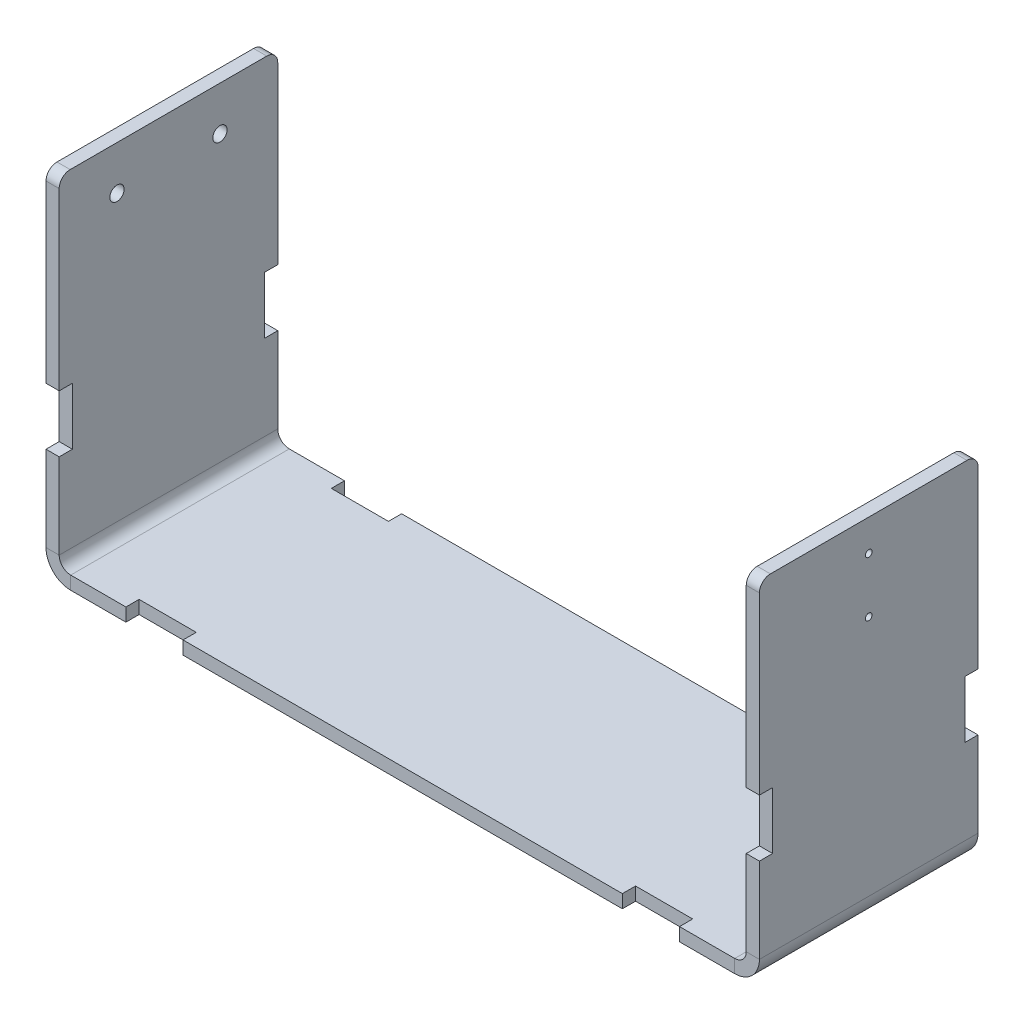
SolidWorks part; units mm, degrees
note: The reader was unsure of these and kept them because the rebuilt part matched: bend radius of "Base-Flange1", "BaseBend1", "BaseBend2".
ref_plane "Front Plane" through (0, 0, 0) normal (0, 0, 1) x (1, 0, 0)
ref_plane "Top Plane" through (0, 0, 0) normal (0, 1, 0) x (1, 0, 0)
ref_plane "Right Plane" through (0, 0, 0) normal (1, 0, 0) x (0, 0, -1)
sketch "Sketch1" plane through (0, 0, 0) normal (0, 0, 1) x (1, 0, 0)
  line L0 (79.4411, 0) -> (-79.4411, 0)
  line L1 (-79.4411, 0) -> (-79.4411, 78.6072)
  line L2 (0, -1000) -> (0, 49000) construction
  line L3 (79.4411, 0) -> (79.4411, 78.6072)
  line L4 (0, 78.6072) -> (-38.1661, 40.4411) construction
  line L5 (-1000, 78.6072) -> (49000, 78.6072) construction
  line L6 (-66.7411, -930.7018) -> (-66.7411, 49069.2982) construction
  circle A0 centre (0, 78.6072) radius 25.4 construction
  circle A1 centre (-38.1661, 40.4411) radius 28.575 construction
  circle A2 centre (0, 78.6072) radius 25.4 construction
  point P7 (0, 0)
  dimension "D1" = 50.8
  dimension "D2" = 57.15
  dimension "D4" = 45
  dimension "D6" = 12.7
base flange "Base-Flange1" sketch "Sketch1" end condition mid plane depth 50.546 reverse direction no thickness 3.048 reverse thickness direction yes bend radius 2.667
bend "BaseBend1" bend radius 2.667 bend angle 90 parameters "D5"=1
bend "BaseBend2" bend radius 2.667 bend angle 90 parameters "D5"=2
sketch "Sketch6" plane through (0, 0, 0) normal (0, 1, 0) x (1, 0, 0)
  line L0 (76.7741, 25.273) -> (-76.7741, 25.273) construction
  line L1 (-64.008, 25.273) -> (-50.8, 25.273)
  line L2 (-64.008, 25.273) -> (-64.008, 22.225)
  line L3 (-64.008, 22.225) -> (-50.8, 22.225)
  line L4 (-50.8, 25.273) -> (-50.8, 22.225)
  line L5 (76.7741, -25.273) -> (-76.7741, -25.273) construction
  line L6 (-64.008, -25.273) -> (-50.8, -25.273)
  line L7 (-64.008, -25.273) -> (-64.008, -22.225)
  line L8 (-64.008, -22.225) -> (-50.8, -22.225)
  line L9 (-50.8, -25.273) -> (-50.8, -22.225)
  line L10 (-1000, 0) -> (49000, 0) construction
  line L11 (0, -1000) -> (0, 49000) construction
  line L24 (50.8, -25.273) -> (50.8, -22.225)
  line L25 (64.008, -22.225) -> (50.8, -22.225)
  line L26 (64.008, -25.273) -> (64.008, -22.225)
  line L27 (64.008, -25.273) -> (50.8, -25.273)
  line L28 (50.8, 25.273) -> (50.8, 22.225)
  line L29 (64.008, 22.225) -> (50.8, 22.225)
  line L30 (64.008, 25.273) -> (64.008, 22.225)
  line L31 (64.008, 25.273) -> (50.8, 25.273)
  dimension "D1" = 13.208
  dimension "D2" = 3.048
  dimension "D3" = 50.8
extrude "Cut-Extrude1" cut sketch "Sketch6" against normal through all both and the other way through all normal cut yes
sketch "Sketch7" plane through (-79.4411, 0, 0) normal (1, 0, 0) x (0, 0, -1)
  line L0 (-25.273, 78.6072) -> (-25.273, 2.667) construction
  line L1 (-25.273, 35.56) -> (-22.225, 35.56)
  line L2 (-25.273, 35.56) -> (-25.273, 22.352)
  line L3 (-25.273, 22.352) -> (-22.225, 22.352)
  line L4 (-22.225, 35.56) -> (-22.225, 22.352)
  line L5 (-25.273, -3.048) -> (25.273, -3.048) construction
  line L6 (0, -1000) -> (0, 49000) construction
  line L7 (22.225, 35.56) -> (22.225, 22.352)
  line L8 (25.273, 22.352) -> (22.225, 22.352)
  line L9 (25.273, 35.56) -> (25.273, 22.352)
  line L10 (25.273, 35.56) -> (22.225, 35.56)
  dimension "D1" = 13.208
  dimension "D2" = 3.048
  dimension "D3" = 25.4
extrude "Cut-Extrude2" cut sketch "Sketch7" against normal through all both and the other way through all normal cut yes
fillet "Fillet1" radius 2.54 4 edges at (80.9651, 78.6072, -25.273) (80.9651, 78.6072, 25.273) (-80.9651, 78.6072, -25.273) (-80.9651, 78.6072, 25.273)
sketch "Sketch8" plane through (79.4411, 0, 0) normal (-1, 0, 0) x (0, 0, 1)
  circle A11 centre (0, 58.6256) radius 0.7747
  circle A12 centre (0, 58.6256) radius 0.7747
  circle A14 centre (0, 71.3256) radius 0.7747
  circle A15 centre (0, 71.3256) radius 0.7747
  dimension "D1" = 1.016
  dimension "D2" = 1.016
extrude "Cut-Extrude3" cut sketch "Sketch8" against normal through all normal cut yes
sketch "Sketch9" [suppressed] plane through (79.4411, 0, 0) normal (-1, 0, 0) x (0, 0, 1)
  circle A0 centre (0, 70.0138) radius 1.5875 construction
  circle A1 centre (0, 70.0138) radius 1.5875
  circle A4 centre (0, 60.4888) radius 0.7747
  circle A5 centre (0, 60.4888) radius 0.7747
  dimension "D1" = 1.016
extrude "Cut-Extrude4" [suppressed] cut sketch "Sketch9" against normal through all
sketch "Sketch10" plane through (-82.4891, 0, 0) normal (-1, 0, 0) x (0, 0, 1)
  circle A5 centre (11.9062, 68.4472) radius 1.651
  circle A6 centre (11.9062, 68.4472) radius 1.651
  circle A8 centre (-11.9063, 68.4472) radius 1.651
  circle A9 centre (-11.9063, 68.4472) radius 1.651
  dimension "D1" = 1.524
  dimension "D2" = 1.524
extrude "Cut-Extrude5" cut sketch "Sketch10" against normal up to next normal cut yes
sketch "Sketch11" [suppressed] plane through (-82.4891, 0, 0) normal (-1, 0, 0) x (0, 0, 1)
  line L0 (0, -925.366) -> (0, 49074.634) construction
  line L1 (-25.273, 35.56) -> (-25.273, 76.0672) construction
  line L2 (25.273, 35.56) -> (25.273, 76.0672) construction
  line L3 (22.733, 78.6072) -> (-22.733, 78.6072) construction
  line L4 (1.778, 33.9032) -> (-1.778, 33.9032)
  line L5 (1.778, 33.9032) -> (1.778, 47.1112)
  line L6 (1.778, 47.1112) -> (-1.778, 47.1112)
  line L7 (-1.778, 33.9032) -> (-1.778, 47.1112)
  line L8 (1.778, 33.9032) -> (-1.778, 47.1112) construction
  line L9 (1.778, 47.1112) -> (-1.778, 33.9032) construction
  point P6 (0, 40.5072)
  dimension "D1" = 3.556
  dimension "D2" = 13.208
  dimension "D3" = 38.1
extrude "Cut-Extrude6" [suppressed] cut sketch "Sketch11" against normal up to next
sketch "Bend-Lines1" [suppressed] plane through (0, 0, 0) normal (0, 1, 0) x (1, 0, 0)
sketch "Bounding-Box1" [suppressed] plane through (0, 0, 0) normal (0, 1, 0) x (1, 0, 0)
sheet metal parameters "Sheet-Metal1" thickness 3.048 parameters "D1"=2.667
flat pattern "Flat-Pattern1" [suppressed]
sketch "Bend-Lines2" plane through (0, -3.048, 0) normal (0, -1, 0) x (-1, 0, 0)
  line L0 (-98.0262, -38.1) -> (-98.0262, 38.1) construction
  line L1 (98.0262, 38.1) -> (98.0262, -38.1) construction
  line L2 (-98.0262, -38.1) -> (-98.0262, 38.1) construction
  line L3 (98.0262, 38.1) -> (98.0262, -38.1) construction
sketch3d "Bounding-Box2" [suppressed]
  line L0 (-97.7692, 76.2, 0) -> (292.5724, 76.2, 0) construction
  line L1 (-97.7692, 0, 0) -> (292.5724, 0, 0) construction
  line L2 (-97.7692, 76.2, 0) -> (-97.7692, 0, 0) construction
  line L3 (292.5724, 76.2, 0) -> (292.5724, 0, 0) construction
bend of the flat pattern "Flatten-<BaseBend1>1"
bend of the flat pattern "Flatten-<BaseBend2>1"
sheet metal parameters "Sheet-Metal2" thickness 3.048 parameters "D1"=2.667
flat pattern "Flat-Pattern1"
sketch "Bend-Lines2" plane through (0, -3.048, 0) normal (0, -1, 0) x (-1, 0, 0)
  line L0 (-98.0262, -38.1) -> (-98.0262, 38.1) construction
  line L1 (98.0262, 38.1) -> (98.0262, -38.1) construction
  line L2 (-98.0262, -38.1) -> (-98.0262, 38.1) construction
  line L3 (98.0262, 38.1) -> (98.0262, -38.1) construction
sketch3d "Bounding-Box2" [suppressed]
  line L0 (-97.7692, 76.2, 0) -> (292.5724, 76.2, 0) construction
  line L1 (-97.7692, 0, 0) -> (292.5724, 0, 0) construction
  line L2 (-97.7692, 76.2, 0) -> (-97.7692, 0, 0) construction
  line L3 (292.5724, 76.2, 0) -> (292.5724, 0, 0) construction
bend of the flat pattern "Flatten-<BaseBend1>1"
bend of the flat pattern "Flatten-<BaseBend2>1"
sheet metal parameters "Sheet-Metal3" thickness 3.048 parameters "D1"=2.667
flat pattern "Flat-Pattern1"
sketch "Bend-Lines2" plane through (0, -3.048, 0) normal (0, -1, 0) x (-1, 0, 0)
  line L0 (-98.0262, -25.273) -> (-98.0262, 25.273) construction
  line L1 (98.0262, 25.273) -> (98.0262, -25.273) construction
  line L2 (-98.0262, -25.273) -> (-98.0262, 25.273) construction
  line L3 (98.0262, 25.273) -> (98.0262, -25.273) construction
sketch3d "Bounding-Box2" [suppressed]
  line L0 (-108.7135, 50.546, 0) -> (303.5167, 50.546, 0) construction
  line L1 (-108.7135, 0, 0) -> (303.5167, 0, 0) construction
  line L2 (-108.7135, 50.546, 0) -> (-108.7135, 0, 0) construction
  line L3 (303.5167, 50.546, 0) -> (303.5167, 0, 0) construction
bend of the flat pattern "Flatten-<BaseBend1>1"
bend of the flat pattern "Flatten-<BaseBend2>1"
sheet metal parameters "Sheet-Metal4" thickness 3.048 parameters "D1"=2.667
flat pattern "Flat-Pattern1"
sketch "Bend-Lines2" plane through (0, -3.048, 0) normal (0, -1, 0) x (-1, 0, 0)
  line L0 (-98.0262, -25.273) -> (-98.0262, 25.273) construction
  line L1 (98.0262, 25.273) -> (98.0262, -25.273) construction
  line L2 (-98.0262, -25.273) -> (-98.0262, 25.273) construction
  line L3 (98.0262, 25.273) -> (98.0262, -25.273) construction
sketch3d "Bounding-Box2" [suppressed]
  line L0 (-108.7135, 50.546, 0) -> (303.5167, 50.546, 0) construction
  line L1 (-108.7135, 0, 0) -> (303.5167, 0, 0) construction
  line L2 (-108.7135, 50.546, 0) -> (-108.7135, 0, 0) construction
  line L3 (303.5167, 50.546, 0) -> (303.5167, 0, 0) construction
bend of the flat pattern "Flatten-<BaseBend1>1"
bend of the flat pattern "Flatten-<BaseBend2>1"
sheet metal parameters "Sheet-Metal5" thickness 3.048 parameters "D1"=2.667
flat pattern "Flat-Pattern1"
sketch "Bend-Lines2" plane through (0, -3.048, 0) normal (0, -1, 0) x (-1, 0, 0)
  line L0 (-98.0262, -25.273) -> (-98.0262, 25.273) construction
  line L1 (98.0262, 25.273) -> (98.0262, -25.273) construction
  line L2 (-98.0262, -25.273) -> (-98.0262, 25.273) construction
  line L3 (98.0262, 25.273) -> (98.0262, -25.273) construction
sketch3d "Bounding-Box2" [suppressed]
  line L0 (-108.7135, 50.546, 0) -> (303.5167, 50.546, 0) construction
  line L1 (-108.7135, 0, 0) -> (303.5167, 0, 0) construction
  line L2 (-108.7135, 50.546, 0) -> (-108.7135, 0, 0) construction
  line L3 (303.5167, 50.546, 0) -> (303.5167, 0, 0) construction
bend of the flat pattern "Flatten-<BaseBend1>1"
bend of the flat pattern "Flatten-<BaseBend2>1"
sheet metal parameters "Sheet-Metal6" thickness 3.048 parameters "D1"=2.667
flat pattern "Flat-Pattern1"
sketch "Bend-Lines2" plane through (0, -3.048, 0) normal (0, -1, 0) x (-1, 0, 0)
  line L0 (-80.0657, -25.273) -> (-80.0657, 25.273) construction
  line L1 (80.0657, 25.273) -> (80.0657, -25.273) construction
  line L2 (-80.0657, -25.273) -> (-80.0657, 25.273) construction
  line L3 (80.0657, 25.273) -> (80.0657, -25.273) construction
sketch3d "Bounding-Box2" [suppressed]
  line L0 (-79.8564, 50.546, 0) -> (238.7386, 50.546, 0) construction
  line L1 (-79.8564, 0, 0) -> (238.7386, 0, 0) construction
  line L2 (-79.8564, 50.546, 0) -> (-79.8564, 0, 0) construction
  line L3 (238.7386, 50.546, 0) -> (238.7386, 0, 0) construction
bend of the flat pattern "Flatten-<BaseBend1>1"
bend of the flat pattern "Flatten-<BaseBend2>1"
sheet metal parameters "Sheet-Metal7" thickness 3.048 parameters "D1"=2.667
flat pattern "Flat-Pattern1"
sketch "Bend-Lines2" plane through (0, -3.048, 0) normal (0, -1, 0) x (-1, 0, 0)
  line L0 (-80.0657, -25.273) -> (-80.0657, 25.273) construction
  line L1 (80.0657, 25.273) -> (80.0657, -25.273) construction
  line L2 (-80.0657, -25.273) -> (-80.0657, 25.273) construction
  line L3 (80.0657, 25.273) -> (80.0657, -25.273) construction
sketch3d "Bounding-Box2" [suppressed]
  line L0 (-79.8564, 50.546, 0) -> (238.7386, 50.546, 0) construction
  line L1 (-79.8564, 0, 0) -> (238.7386, 0, 0) construction
  line L2 (-79.8564, 50.546, 0) -> (-79.8564, 0, 0) construction
  line L3 (238.7386, 50.546, 0) -> (238.7386, 0, 0) construction
bend of the flat pattern "Flatten-<BaseBend1>1"
bend of the flat pattern "Flatten-<BaseBend2>1"
equation "\"D2@Base-Flange1\"=1.750000in + 0.24in"
